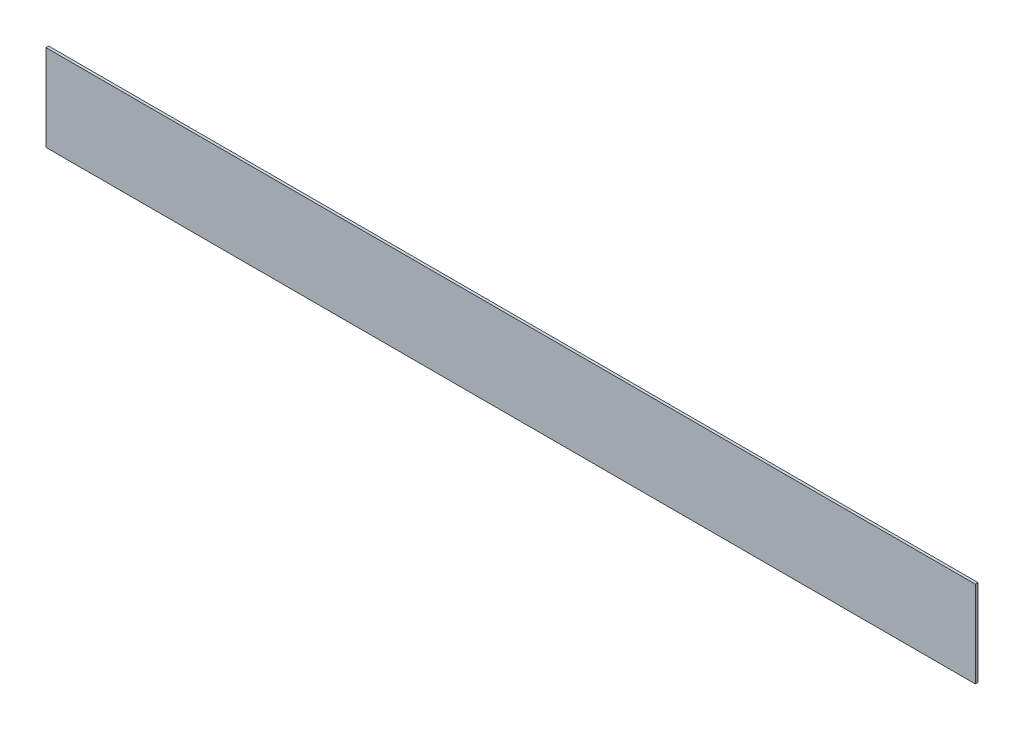
SolidWorks part; units mm, degrees
ref_plane "Front Plane" through (0, 0, 0) normal (0, 0, 1) x (1, 0, 0)
ref_plane "Top Plane" through (0, 0, 0) normal (0, 1, 0) x (1, 0, 0)
ref_plane "Right Plane" through (0, 0, 0) normal (1, 0, 0) x (0, 0, -1)
sketch "Sketch1" plane through (0, 0, 0) normal (0, 0, 1) x (1, 0, 0)
  line L1 (0, 0) -> (546.1, 0)
  line L2 (0, 0) -> (0, 50.8)
  line L3 (0, 50.8) -> (546.1, 50.8)
  line L4 (546.1, 0) -> (546.1, 50.8)
  dimension "D1" = 546.1
  dimension "D2" = 50.8
extrude "Boss-Extrude1" add sketch "Sketch1" along normal blind 1.5875
